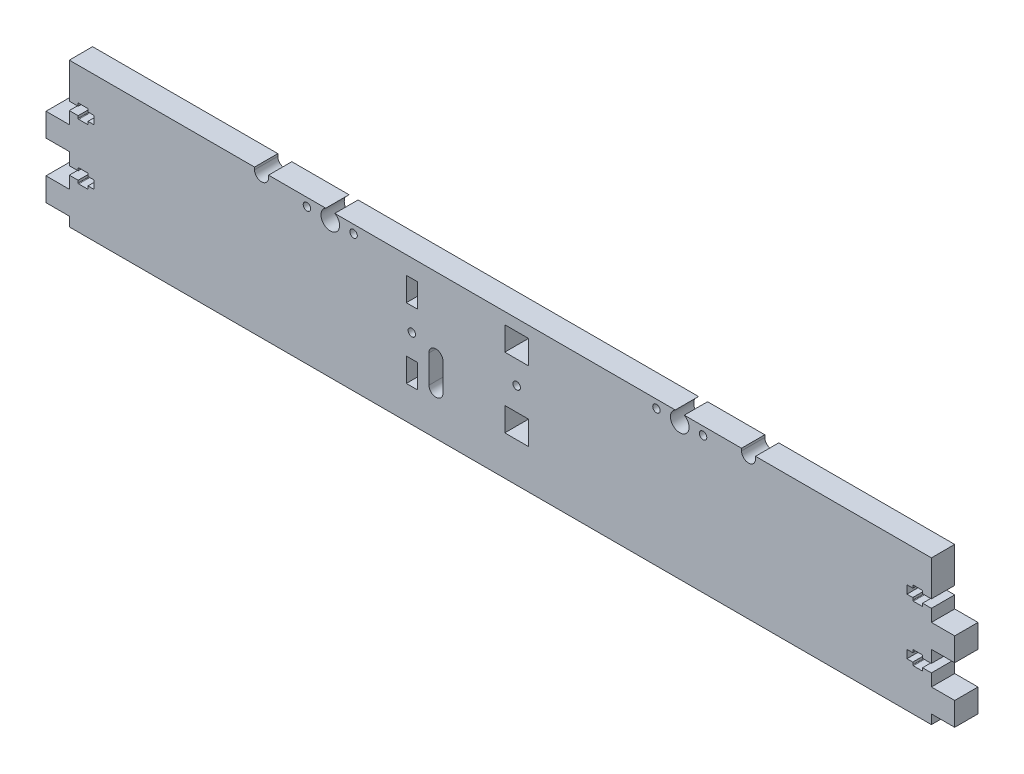
SolidWorks part; units mm, degrees
ref_plane "Front Plane" through (0, 0, 0) normal (0, 0, 1) x (1, 0, 0)
ref_plane "Top Plane" through (0, 0, 0) normal (0, 1, 0) x (1, 0, 0)
ref_plane "Right Plane" through (0, 0, 0) normal (1, 0, 0) x (0, 0, -1)
sketch "Sketch1" plane through (0, 0, 0) normal (0, 0, 1) x (1, 0, 0)
  line L0 (0, 0) -> (-185, 0)
  line L1 (-185, 0) -> (-185, -62) construction
  line L2 (0, -62) -> (-185, -62)
  line L3 (-185, -62) -> (-185, -58)
  line L4 (-185, -58) -> (-195, -58)
  line L5 (-195, -58) -> (-195, -48)
  line L6 (-195, -48) -> (-185, -48)
  line L7 (-185, -48) -> (-185, -34)
  line L8 (-185, -34) -> (-195, -34)
  line L9 (-195, -34) -> (-195, -24)
  line L10 (-195, -24) -> (-185, -24)
  line L11 (0, -62) -> (0, 0)
  line L12 (-185, -24) -> (-185, 0)
  line L13 (-195, -58) -> (-195, -24) construction
  line L14 (-195, -29) -> (-185, -29) construction
  line L15 (-195, -53) -> (-185, -53) construction
  dimension "D3" = 10
  dimension "D1" = 185
  dimension "D2" = 10
  dimension "D4" = 10
  dimension "D5" = 24
  dimension "D6" = 29
  dimension "D7" = 62
extrude "MainBody" add sketch "Sketch1" along normal blind 10
sketch "Sketch3" plane through (0, 0, 10) normal (0, 0, 1) x (1, 0, 0)
  line L0 (-185, -17) -> (-174.5, -17) construction
  line L1 (-185, 0) -> (-185, -24) construction
  line L2 (-185, -18.75) -> (-181.2, -18.75)
  line L3 (-181.2, -18.75) -> (-181.2, -19.75)
  line L4 (-180.95, -20) -> (-177.25, -20)
  line L5 (-177, -19.75) -> (-177, -18.75)
  line L6 (-177, -18.75) -> (-174.5, -18.75)
  line L7 (-174.5, -18.75) -> (-174.5, -15.25)
  line L8 (-181.2, -18.75) -> (-177, -18.75) construction
  line L9 (-195, -24) -> (-195, -34) construction
  line L10 (-181.2, -15.25) -> (-177, -15.25) construction
  line L11 (-177, -15.25) -> (-174.5, -15.25)
  line L12 (-177, -14.25) -> (-177, -15.25)
  line L13 (-180.95, -14) -> (-177.25, -14)
  line L14 (-181.2, -15.25) -> (-181.2, -14.25)
  line L15 (-185, -15.25) -> (-181.2, -15.25)
  line L16 (-185, -18.75) -> (-185, -15.25)
  line L17 (-185, -24) -> (-185, -34) construction
  line L19 (-195, -24) -> (-195, -34) construction
  line L20 (-195, -29) -> (-185, -29) construction
  line L21 (-181.2, -42.75) -> (-177, -42.75) construction
  line L22 (-181.2, -39.25) -> (-177, -39.25) construction
  line L23 (-185, -41) -> (-174.5, -41) construction
  line L24 (-185, -39.25) -> (-185, -42.75)
  line L25 (-185, -42.75) -> (-181.2, -42.75)
  line L26 (-181.2, -42.75) -> (-181.2, -43.75)
  line L27 (-180.95, -44) -> (-177.25, -44)
  line L28 (-177, -43.75) -> (-177, -42.75)
  line L29 (-177, -42.75) -> (-174.5, -42.75)
  line L30 (-174.5, -39.25) -> (-174.5, -42.75)
  line L31 (-177, -39.25) -> (-174.5, -39.25)
  line L32 (-177, -38.25) -> (-177, -39.25)
  line L33 (-180.95, -38) -> (-177.25, -38)
  line L34 (-181.2, -39.25) -> (-181.2, -38.25)
  line L35 (-185, -39.25) -> (-181.2, -39.25)
  line L36 (-181.2, -15.25) -> (-177, -15.25) construction
  arc A0 (-177.25, -20) -> (-177, -19.75) centre (-177.25, -19.75) ccw
  arc A1 (-181.2, -19.75) -> (-180.95, -20) centre (-180.95, -19.75) ccw
  arc A2 (-181.2, -14.25) -> (-180.95, -14) centre (-180.95, -14.25) cw
  arc A3 (-177.25, -14) -> (-177, -14.25) centre (-177.25, -14.25) cw
  arc A4 (-177.25, -44) -> (-177, -43.75) centre (-177.25, -43.75) ccw
  arc A5 (-181.2, -43.75) -> (-180.95, -44) centre (-180.95, -43.75) ccw
  arc A6 (-181.2, -38.25) -> (-180.95, -38) centre (-180.95, -38.25) cw
  arc A7 (-177.25, -38) -> (-177, -38.25) centre (-177.25, -38.25) cw
  point P6 (-195, -29)
  point P15 (-177, -20)
  point P18 (-181.2, -20)
  point P29 (-181.2, -14)
  point P30 (-177, -14)
  point P62 (-177, -44)
  point P63 (-181.2, -44)
  point P64 (-181.2, -38)
  point P65 (-177, -38)
  dimension "D2" = 8
  dimension "D7" = 0.25
  dimension "D1" = 10.5
  dimension "D3" = 1.75
  dimension "D4" = 3
  dimension "D5" = 12
  dimension "D6" = 4.2
extrude "ScrewCutouts" cut sketch "Sketch3" against normal through all
mirror "Mirror1" about plane through (0, 0, 0) normal (1, 0, 0) of "ScrewCutouts", "MainBody"
sketch "Sketch2" plane through (0, 0, 10) normal (0, 0, 1) x (1, 0, 0)
  line L0 (0, 0) -> (0, -62) construction
  line L1 (-185, -62) -> (185, -62) construction
  line L2 (2, 0) -> (2, -62) construction
  line L3 (185, 0) -> (-185, 0) construction
  line L4 (-63, -3.5) -> (-83, -3.5) construction
  line L5 (-73, -7.5) -> (-73, 0.5) construction
  line L6 (77, -7.5) -> (77, 0.5) construction
  line L7 (67, -3.5) -> (87, -3.5) construction
  circle A0 centre (-73, -3.5) radius 4
  circle A1 centre (-83, -3.5) radius 1.6
  circle A2 centre (-63, -3.5) radius 1.6
  circle A3 centre (67, -3.5) radius 1.6
  circle A4 centre (87, -3.5) radius 1.6
  circle A5 centre (77, -3.5) radius 4
  dimension "D1" = 3.2
  dimension "D2" = 8
  dimension "D3" = 10
  dimension "D4" = 3.5
  dimension "D5" = 75
  dimension "D6" = 2
extrude "RodCutouts" cut sketch "Sketch2" against normal through all
sketch "Sketch4" plane through (0, 0, 10) normal (0, 0, 1) x (1, 0, 0)
  line L0 (77, -3.5) -> (-73, -3.5) construction
  line L1 (2, -3.5) -> (2, -62) construction
  line L2 (-185, -62) -> (185, -62) construction
  line L3 (7, -45.1) -> (7, -4.9) construction
  line L4 (75.0635, 0) -> (-71.0635, 0) construction
  line L5 (7, -10) -> (7, -40) construction
  line L6 (1.9, -4.9) -> (12.1, -4.9)
  line L7 (1.9, -4.9) -> (1.9, -15.1)
  line L8 (1.9, -15.1) -> (12.1, -15.1)
  line L9 (12.1, -4.9) -> (12.1, -15.1)
  line L10 (1.9, -4.9) -> (12.1, -15.1) construction
  line L11 (1.9, -15.1) -> (12.1, -4.9) construction
  line L12 (1.9, -34.9) -> (12.1, -34.9)
  line L13 (1.9, -34.9) -> (1.9, -45.1)
  line L14 (1.9, -45.1) -> (12.1, -45.1)
  line L15 (12.1, -34.9) -> (12.1, -45.1)
  line L16 (1.9, -34.9) -> (12.1, -45.1) construction
  line L17 (1.9, -45.1) -> (12.1, -34.9) construction
  circle A0 centre (7, -25) radius 1.6
  point P12 (7, -10)
  point P17 (7, -40)
  dimension "D8" = 3.2
  dimension "D1" = 10.2
  dimension "D2" = 10.2
  dimension "D3" = 10.2
  dimension "D4" = 10.2
  dimension "D5" = 30
  dimension "D6" = 10
  dimension "D7" = 5
extrude "Cut-Extrude3" cut sketch "Sketch4" against normal through all
sketch "Sketch5" plane through (0, 0, 10) normal (0, 0, 1) x (1, 0, 0)
  line L0 (-38, 0) -> (-38, -62) construction
  line L1 (-74.9365, 0) -> (-185, 0) construction
  line L2 (-185, -62) -> (185, -62) construction
  line L3 (-40.35, -17.85) -> (-40.35, -37.65) construction
  line L4 (-40.35, -7.65) -> (-35.65, -7.65)
  line L5 (-40.35, -7.65) -> (-40.35, -17.85)
  line L6 (-40.35, -17.85) -> (-35.65, -17.85)
  line L7 (-35.65, -7.65) -> (-35.65, -17.85)
  line L8 (-40.35, -7.65) -> (-35.65, -17.85) construction
  line L9 (-40.35, -17.85) -> (-35.65, -7.65) construction
  line L10 (-40.35, -37.65) -> (-35.65, -37.65)
  line L11 (-40.35, -37.65) -> (-40.35, -47.85)
  line L12 (-40.35, -47.85) -> (-35.65, -47.85)
  line L13 (-35.65, -37.65) -> (-35.65, -47.85)
  line L14 (-40.35, -37.65) -> (-35.65, -47.85) construction
  line L15 (-40.35, -47.85) -> (-35.65, -37.65) construction
  line L16 (-35.65, -37.65) -> (-35.65, -17.85) construction
  line L17 (-40.35, -27.75) -> (-35.65, -27.75) construction
  line L18 (-73, -3.5) -> (77, -3.5) construction
  line L19 (2, -3.5) -> (2, -62) construction
  line L20 (2, -32.75) -> (-195, -32.75) construction
  line L21 (-195, -24) -> (-195, -34) construction
  circle A0 centre (-38, -27.75) radius 1.6
  point P6 (-38, -12.75)
  point P11 (-38, -42.75)
  dimension "D3" = 10.2
  dimension "D4" = 10.2
  dimension "D5" = 30
  dimension "D6" = 3.2
  dimension "D1" = 4.7
  dimension "D2" = 0
  dimension "D7" = 40
  dimension "D8" = 5
extrude "EndstopHolder" cut sketch "Sketch5" against normal through all
sketch "Sketch6" plane through (0, 0, 10) normal (0, 0, 1) x (1, 0, 0)
  line L0 (-40.35, -37.65) -> (-40.35, -17.85) construction
  line L1 (-42.35, -37.65) -> (-27.65, -37.65) construction
  line L3 (-27.65, -43.65) -> (-27.65, -31.65) construction
  line L4 (-30.65, -43.65) -> (-30.65, -31.65)
  line L5 (-24.65, -43.65) -> (-24.65, -31.65)
  line L6 (-35.65, -37.65) -> (-40.35, -37.65) construction
  line L7 (-35.65, -47.85) -> (-35.65, -37.65) construction
  arc A0 (-30.65, -43.65) -> (-24.65, -43.65) centre (-27.65, -43.65) ccw
  arc A1 (-24.65, -31.65) -> (-30.65, -31.65) centre (-27.65, -31.65) ccw
  point P10 (-27.65, -37.65)
  dimension "D1" = 3
  dimension "D2" = 12
  dimension "D3" = 8
  dimension "D4" = 0
extrude "EndstopWires" cut sketch "Sketch6" against normal through all
sketch "Sketch7" plane through (0, 0, 10) normal (0, 0, 1) x (1, 0, 0)
  line L0 (-73, -3.5) -> (77, -3.5) construction
  line L1 (2, -3.5) -> (2, -62) construction
  line L3 (-102.5, 0) -> (-102.5, -1) construction
  line L4 (-74.9365, 0) -> (-185, 0) construction
  line L5 (-99.5, 0) -> (-99.5, -1)
  line L6 (-105.5, 0) -> (-105.5, -1)
  line L7 (106.5, 0) -> (106.5, -1) construction
  line L8 (103.5, 0) -> (103.5, -1)
  line L9 (109.5, 0) -> (109.5, -1)
  line L10 (-185, -62) -> (185, -62) construction
  arc A0 (-99.5, 0) -> (-105.5, 0) centre (-102.5, 0) ccw
  arc A1 (-105.5, -1) -> (-99.5, -1) centre (-102.5, -1) ccw
  arc A2 (103.5, 0) -> (109.5, 0) centre (106.5, 0) cw
  arc A3 (109.5, -1) -> (103.5, -1) centre (106.5, -1) cw
  point P12 (-102.5, -0.5)
  point P19 (106.5, -0.5)
  dimension "D3" = 3
  dimension "D1" = 1
  dimension "D2" = 104.5
extrude "Cut-Extrude4" cut sketch "Sketch7" against normal through all
equation "\"Y-ROD-SPACING\"=75"
equation "\"D5@Sketch2\"=\"Y-ROD-SPACING\""
equation "\"Y-BED-OFFSET\"=2"
equation "\"D6@Sketch2\"=\"Y-BED-OFFSET\""
equation "\"T-SLOT-NUT-FILLET-RADIUS\"=0.25"
equation "\"D7@Sketch3\"=\"T-SLOT-NUT-FILLET-RADIUS\""
equation "\"T-SLOT-SCREW-SHAFT-RADIUS\"=1.75"
equation "\"D3@Sketch3\"=\"T-SLOT-SCREW-SHAFT-RADIUS\""
equation "\"T-SLOT-SCREW-SHAFT-CUTOUT-LENGTH\"=10.5"
equation "\"D1@Sketch3\"=\"T-SLOT-SCREW-SHAFT-CUTOUT-LENGTH\""
equation "\"T-SLOT-NUT-DEPTH\"=4.2"
equation "\"D6@Sketch3\"=\"T-SLOT-NUT-DEPTH\""
equation "\"T-SLOT-NUT-WIDTH\"=3"
equation "\"D4@Sketch3\"=\"T-SLOT-NUT-WIDTH\""
equation "\"T-SLOT-NUT-END-DISTANCE\"=8"
equation "\"D2@Sketch3\"=\"T-SLOT-NUT-END-DISTANCE\""
equation "\"ACRYLIC-TAB-CUTOUT-SIZE\"=\"ACRYLIC-THICKNESS\"+\"ACRYLIC-TAB-TOLERANCE\"*2"
equation "\"D1@Sketch4\"=\"ACRYLIC-TAB-CUTOUT-SIZE\""
equation "\"D2@Sketch4\"=\"ACRYLIC-TAB-CUTOUT-SIZE\""
equation "\"D3@Sketch4\"=\"ACRYLIC-TAB-CUTOUT-SIZE\""
equation "\"D4@Sketch4\"=\"ACRYLIC-TAB-CUTOUT-SIZE\""
equation "\"ACRYLIC-M3-HOLE\"=3.2"
equation "\"D8@Sketch4\"=\"ACRYLIC-M3-HOLE\""
equation "\"Y-BED-ROD-INSET\"=3.5"
equation "\"D1@Sketch2\"=\"ACRYLIC-M3-HOLE\""
equation "\"D4@Sketch2\"=\"Y-BED-ROD-INSET\""
equation "\"SMOOTHROD-CAP-SCREW-DISTANCE\"=20"
equation "\"D3@Sketch2\"=\"SMOOTHROD-CAP-SCREW-DISTANCE\"/2"
equation "\"ACRYLIC-TAB-WIDTH\"=\"ACRYLIC-THICKNESS\""
equation "\"FRAME-WIDTH-INNER\"=370"
equation "\"D2@Sketch1\"=\"ACRYLIC-TAB-WIDTH\""
equation "\"D3@Sketch1\"=\"ACRYLIC-TAB-WIDTH\""
equation "\"D4@Sketch1\"=\"ACRYLIC-TAB-WIDTH\""
equation "\"D1@Sketch1\"=\"FRAME-WIDTH-INNER\"/2"
equation "\"X-ROD-SPACING\"=45"
equation "\"Z-ROD-SPACING\"=17.5"
equation "\"ACRYLIC-THICKNESS\"=10"
equation "\"ACRYLIC-THICKNESS2\"=4.5"
equation "\"NEMA17-HOLE-SPACING\"=31"
equation "\"NEMA17-CENTRAL-CUTOUT\"=22.5"
equation "\"Z-BRACKET-REACH\"=55"
equation "\"TOP-BRACKET-SPACING\"=40"
equation "\"SMOOTHROD-X-LENGTH\"=350"
equation "\"SMOOTHROD-Y-LENGTH\"=350"
equation "\"SMOOTHROD-Z-LENGTH\"=350"
equation "\"SMOOTHROD-TIGHTENING-HEADROOM\"=1"
equation "\"LEADSCREW-Z-LENGTH\"=300"
equation "\"SCREW-LENGTH-FRAME\"=\"ACRYLIC-THICKNESS\" + 10"
equation "\"SCREW-HEAD-RADIUS\"=6"
equation "\"PRINTED-X-SMOOTHROD-DIAMETER\"=8.2"
equation "\"PRINTED-X-SMOOTHROD-CUTOUT\"=10"
equation "\"PRINTED-X-BASE-HEIGHT\"=10"
equation "\"PRINTED-LM8UU-CUTOUT-SIZE\"=16"
equation "\"PRINTED-LM8UU-CUTOUT-LENGTH\"=24.5"
equation "\"PRINTED-X-IDLER-HEIGHT\"=16"
equation "\"PSU-MOUNTING-WIDTH\"=95"
equation "\"PSU-MOUNTING-HEIGHT\"=177"
equation "\"D1@MainBody\"=\"ACRYLIC-THICKNESS\""
equation "\"D1@Sketch5\"=\"ACRYLIC-THICKNESS2\"+\"ACRYLIC-TAB-TOLERANCE\"*2"
equation "\"D3@Sketch5\"=\"ACRYLIC-TAB-CUTOUT-SIZE\""
equation "\"D4@Sketch5\"=\"ACRYLIC-TAB-CUTOUT-SIZE\""
equation "\"D6@Sketch5\"=\"ACRYLIC-M3-HOLE\""
equation "\"Y-BED-SCREW-SPACING\"=209"
equation "\"Y-BED-SCREW-CUTOUT-SLOT-HEIGHT\"=1"
equation "\"Z-ROD-INSET\"=16"
equation "\"Y-BELT-TO-ROD-DISTANCE\"=20"
equation "\"SPOOL-HOLDER-ROD-SPACING\"=150"
equation "\"D1@Sketch7\"=\"Y-BED-SCREW-CUTOUT-SLOT-HEIGHT\""
equation "\"D2@Sketch7\"=\"Y-BED-SCREW-SPACING\"/2"
equation "\"ACRYLIC-TAB-TOLERANCE\"=.1"
equation "\"SCREW-LENGTH-MOTOR\"=\"ACRYLIC-THICKNESS\" + 5"
equation "\"SCREW-LENGTH-EXTRUDER\"=28"
equation "\"ACRYLIC-X-CARRIAGE-WIDTH\"=55"
equation "\"ACRYLIC-X-CARRIAGE-HEIGHT\"=75"
equation "\"ACRYLIC-X-CARRIAGE-LM8UU-CUTOUT-WIDTH\"=24.25"
equation "\"ACRYLIC-X-CARRIAGE-SCREW-SPACING-X\"=15"
equation "\"ACRYLIC-X-CARRIAGE-SCREW-SPACING-Y\"=33"
equation "\"ACRYLIC-X-CARRIAGE-CENTER-TAB-SPACING\"=14"
equation "\"ACRYLIC-X-CARRIAGE-EXTRUDER-OFFSET\"=26"
equation "\"ACRYLIC-X-CARRIAGE-EXTRUDER-ANGLE\"=90"
equation "\"ACRYLIC-X-CARRIAGE-EXTRUDER-SHELF-DEPTH\"=\"ACRYLIC-X-CARRIAGE-EXTRUDER-OFFSET\" + 30"
equation "\"ACRYLIC-X-CARRIAGE-EXTRUDER-BRACE-SPACING\"=23"
equation "\"ACRYLIC-X-CARRIAGE-EXTRUDER-BRACE-TAB-OFFSET\"=20"
equation "\"ACRYLIC-X-CARRIAGE-EXTRUDER-BRACE-HEIGHT\"=35"
equation "\"ACRYLIC-X-CARRIAGE-EXTRUDER-BRACE-SCREW-SPACING\"=22"
